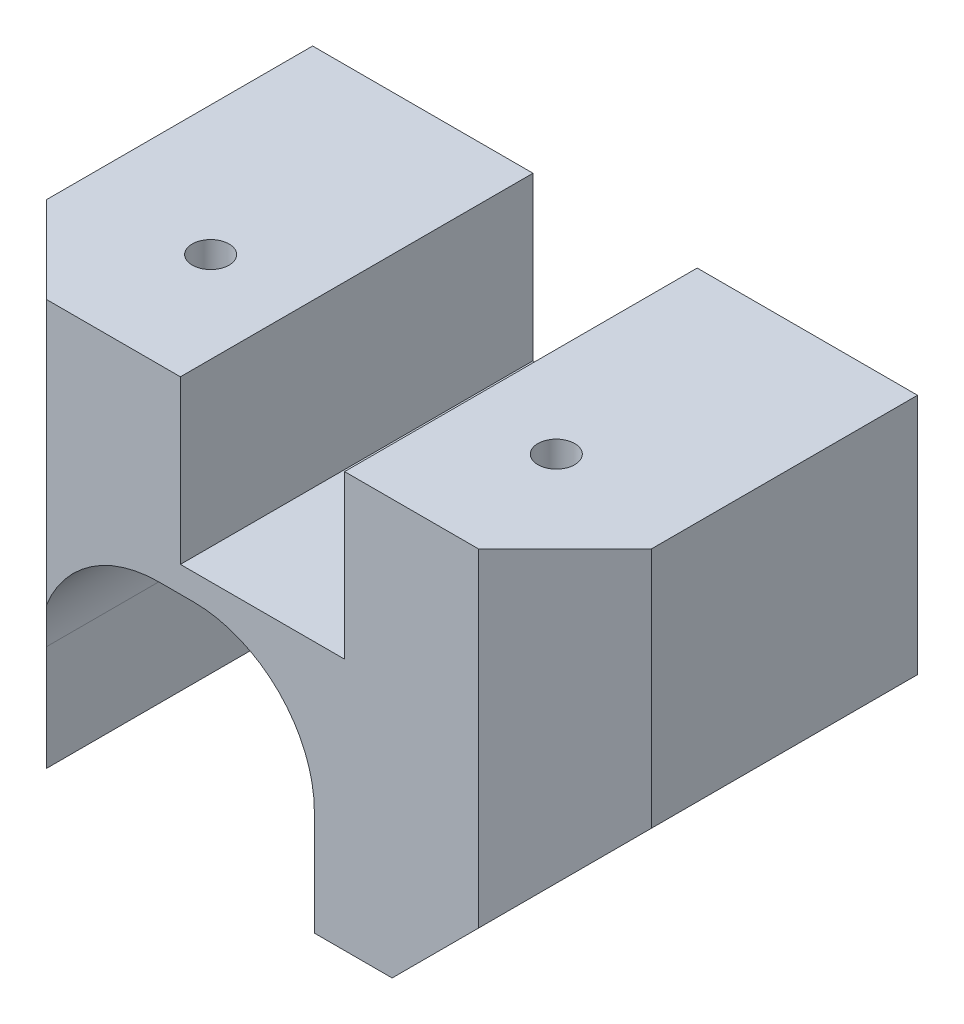
SolidWorks part; units mm, degrees
material "Nylon 6/10"
ref_plane "Front Plane" through (0, 0, 0) normal (0, 0, 1) x (1, 0, 0)
ref_plane "Top Plane" through (0, 0, 0) normal (0, 1, 0) x (1, 0, 0)
ref_plane "Right Plane" through (0, 0, 0) normal (1, 0, 0) x (0, 0, -1)
sketch "Sketch1" plane through (0, 0, 0) normal (0, 1, 0) x (1, 0, 0)
  line L1 (-22.225, -12.954) -> (22.225, -12.954)
  line L2 (-22.225, -12.954) -> (-22.225, 12.954)
  line L3 (-22.225, 12.954) -> (22.225, 12.954)
  line L4 (22.225, -12.954) -> (22.225, 12.954)
  line L5 (-22.225, -12.954) -> (22.225, 12.954) construction
  line L6 (-22.225, 12.954) -> (22.225, -12.954) construction
  point P0 (0, 0)
  dimension "D1" = 25.908
  dimension "D2" = 44.45
extrude "Boss-Extrude1" add sketch "Sketch1" along normal blind 30.48
chamfer "SideChamfer" distance 12.7 angle 45 1 edges at (22.225, 0, 0)
chamfer "BackChamfers" distance 6.35 angle 45 2 edges at (-22.225, 15.24, 12.954) (22.225, 21.59, 12.954)
sketch "Sketch2" plane through (0, 0, 12.954) normal (0, 0, 1) x (1, 0, 0)
  line L1 (-6.0325, 30.48) -> (6.0325, 30.48)
  line L2 (-6.0325, 30.48) -> (-6.0325, 18.542)
  line L3 (-6.0325, 18.542) -> (6.0325, 18.542)
  line L4 (6.0325, 30.48) -> (6.0325, 18.542)
  line L5 (-6.0325, 30.48) -> (6.0325, 18.542) construction
  line L6 (-6.0325, 18.542) -> (6.0325, 30.48) construction
  line L7 (0, 18.542) -> (0, 30.48) construction
  line L8 (-15.875, 30.48) -> (15.875, 30.48) construction
  point P0 (0, 24.511)
  dimension "D1" = 11.938
  dimension "D2" = 12.065
extrude "LinActSlot" cut sketch "Sketch2" against normal through all
hole_wizard "MoutingHoles" positions "Sketch4" profile "Sketch3" tap size "#6-32" standard "ANSI Inch"
sketch "Sketch4" plane through (14.1604, 30.48, 8.3734) normal (0, -1, 0) x (-1, 0, 0)
  line L0 (14.1604, 8.3734) -> (14.1604, 11.4563) construction
  line L3 (30.0354, -4.5806) -> (20.1929, -4.5806) construction
  point P0 (1.4604, 4.3094)
  point P2 (26.8604, 4.3094)
  dimension "D1" = 25.4
  dimension "D2" = 8.89
sketch "Sketch3" plane through (12.7, 30.48, 4.064) normal (1, 0, 0) x (0, 0, 1)
  line L0 (0, 0) -> (0, 15.2907)
  line L1 (0, 15.2907) -> (1.3525, 14.478)
  line L2 (1.3525, 14.478) -> (1.3525, 0)
  line L5 (1.3525, 0) -> (0, 0)
  line L10 (0, 15.2907) -> (-1.3526, 14.478) construction
  line L11 (0, -6.35) -> (0, 107.95) construction
  dimension "Tap Drill Dia." = 2.7051
  dimension "Tap Drill Depth" = 14.478
  dimension "Drill Angle" = 118
sketch "Sketch5" plane through (0, 0, -12.954) normal (0, 0, -1) x (-1, 0, 0)
  line L0 (-9.525, 0) -> (22.225, 0) construction
  line L2 (16.51, 0) -> (-3.81, 0)
  line L3 (16.51, 0) -> (16.51, 7.747)
  line L4 (7.62, 16.637) -> (5.08, 16.637)
  line L6 (-3.81, 0) -> (-3.81, 7.747)
  line L8 (22.225, 30.48) -> (22.225, 0) construction
  arc A0 (-3.81, 7.747) -> (5.08, 16.637) centre (5.08, 7.747) cw
  arc A1 (16.51, 7.747) -> (7.62, 16.637) centre (7.62, 7.747) ccw
  point P8 (6.35, 0)
  dimension "D2" = 16.637
  dimension "D4" = 8.89
  dimension "D1" = 20.32
  dimension "D3" = 15.875
extrude "MotorSlot" cut sketch "Sketch5" against normal through all
hole_wizard "MotorMountingHoles" positions "Sketch7" profile "Sketch6" tap size "#4-40" standard "ANSI Inch"
sketch "Sketch7" plane through (0, 0, -12.954) normal (0, 0, -1) x (-1, 0, 0)
  line L2 (7.62, 16.637) -> (5.08, 16.637) construction
  line L3 (7.62, 16.637) -> (5.08, 16.637) construction
  line L4 (6.35, 16.637) -> (6.35, -5.5191) construction
  line L6 (6.0325, 30.48) -> (22.225, 30.48) construction
  point P0 (18.8468, 6.35)
  point P8 (-6.1468, 6.35)
  dimension "D1" = 24.13
  dimension "D3" = 24.9936
sketch "Sketch6" plane through (-18.8468, 6.35, -12.954) normal (1, 0, 0) x (0, 1, 0)
  line L0 (0, 0) -> (0, 9.5692)
  line L1 (0, 9.5692) -> (1.1303, 8.89)
  line L2 (1.1303, 8.89) -> (1.1303, 0)
  line L5 (1.1303, 0) -> (0, 0)
  line L10 (0, 9.5692) -> (-1.1303, 8.89) construction
  line L11 (0, -6.35) -> (0, 107.95) construction
  dimension "Tap Drill Dia." = 2.2606
  dimension "Tap Drill Depth" = 8.89
  dimension "Drill Angle" = 118
cosmetic thread "Hole Thread1" parameters "D1"=6.858, "D2"=2.8448
cosmetic thread "Hole Thread2" parameters "D1"=6.858, "D2"=2.8448
